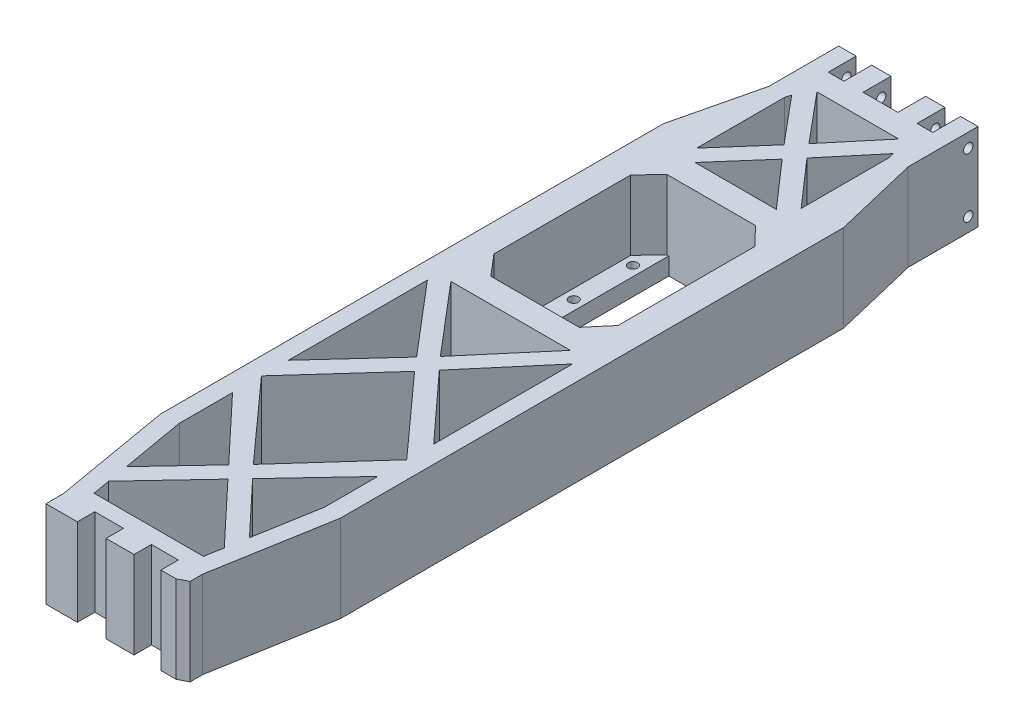
SolidWorks part; units mm, degrees
material "ABS"
ref_plane "Płaszczyzna przednia" through (0, 0, 0) normal (0, 0, 1) x (1, 0, 0)
ref_plane "Płaszczyzna górna" through (0, 0, 0) normal (0, 1, 0) x (1, 0, 0)
ref_plane "Płaszczyzna prawa" through (0, 0, 0) normal (1, 0, 0) x (0, 0, -1)
sketch "Szkic1" plane through (0, 0, 0) normal (0, 1, 0) x (1, 0, 0)
  line L0 (10, 165.9692) -> (14.5, 165.9692)
  line L1 (-0.5, 106.3963) -> (-0.5, -48.6037) construction
  line L2 (-5.4951, 173.9692) -> (-5.4951, 165.9692)
  line L3 (-5.4951, 165.9692) -> (4.4951, 165.9692)
  line L4 (19.5, -48.6037) -> (-20.5, -48.6037)
  line L5 (-11, 173.9692) -> (-5.4951, 173.9692)
  line L6 (25.3521, 129.4864) -> (25.3521, -14.9151)
  line L7 (-11, 173.9692) -> (-11, 165.9692)
  line L8 (14.5, 165.9692) -> (14.5, 173.9692)
  line L9 (-12.7, 117.3963) -> (11.7, 117.3963)
  line L10 (-20.5, 153.94) -> (-26.3521, 129.4864)
  line L11 (14.5, 173.9692) -> (19.5, 173.9692)
  line L12 (-37.6655, 105.3963) -> (36.6655, 105.3963) construction
  line L13 (-0.5, 105.3963) -> (-0.5, 211.3963) construction
  line L14 (11.7, 117.3963) -> (11.7, 72.3963)
  line L15 (11.7, 72.3963) -> (-12.7, 72.3963)
  line L16 (19.5, 173.9692) -> (19.5, 153.94)
  line L17 (-13.2, 117.3963) -> (12.2, 117.3963)
  line L18 (-26.3521, 105.3963) -> (25.3521, 105.3963) construction
  line L19 (1.0907, -6.7501) -> (1.0723, -6.7223)
  line L20 (17.3, 112.0706) -> (17.3, 72.7963)
  line L21 (-20.5, 173.9692) -> (-20.5, 153.94)
  line L22 (19.5, 153.94) -> (25.3521, 129.4864)
  line L23 (10, 173.9692) -> (10, 165.9692)
  line L24 (10, 173.9692) -> (4.4951, 173.9692)
  line L25 (17.3, 72.7963) -> (12.2, 66.7963)
  line L26 (4.4951, 173.9692) -> (4.4951, 165.9692)
  line L27 (12.2, 66.7963) -> (-13.2, 66.7963)
  line L28 (12.2, 117.3963) -> (17.3, 112.0706)
  line L29 (-13.2, 117.3963) -> (-18.3, 112.0706)
  line L30 (-18.3, 72.7963) -> (-13.2, 66.7963)
  line L31 (-18.3, 112.0706) -> (-18.3, 72.7963)
  line L32 (-12.7, 117.3963) -> (-12.7, 72.3963)
  line L33 (19.5, -48.6037) -> (25.3521, -14.9151)
  line L34 (-15.5, 173.9692) -> (-20.5, 173.9692)
  line L35 (-15.5, 165.9692) -> (-15.5, 173.9692)
  line L36 (1.1229, -6.7586) -> (1.0907, -6.7501)
  line L37 (-11, 165.9692) -> (-15.5, 165.9692)
  line L38 (-20.5, -48.6037) -> (-26.3521, -14.9151)
  line L39 (-26.3521, 129.4864) -> (-26.3521, -14.9151)
  line L46 (-2.1229, -6.7586) -> (-2.0907, -6.7501)
  circle A0 centre (14.5, 109.8963) radius 1.35
  circle A1 centre (-0.5, 105.3963) radius 4
  circle A2 centre (14.5, 92.8963) radius 1.35
  circle A3 centre (14.5, 75.8963) radius 1.35
  circle A4 centre (8, 69.5963) radius 1.35
  circle A5 centre (-9, 69.5963) radius 1.35
  circle A7 centre (-15.5, 75.8963) radius 1.35
  circle A8 centre (-15.5, 92.8963) radius 1.35
  circle A9 centre (-15.5, 109.8963) radius 1.35
  point P9 (-15.5208, -48.1484)
  point P12 (0, 85)
  point P14 (-0.5, 156.3785)
  point P16 (-0.5, -39.3616)
  point P18 (-34.2569, 59.805)
  point P22 (-0.5, 105.3963)
  point P24 (-0.5, 176.9822)
  point P27 (32.5, 54.0178)
  point P34 (-0.5, 105.3963)
  point P41 (-0.5, 148.8753)
  point P44 (-0.5, 211.3963)
  point P45 (-9.988, 152.4054)
  point P47 (-36.488, 132.4054)
  point P71 (-0.5, 66.7963)
  point P73 (-0.5, 72.3963)
  point P74 (-0.5, 117.3963)
  point P80 (-0.5, 165.9692)
  point P89 (14.5208, -48.1484)
  dimension "D6" = 45
  dimension "D5" = 12.2
  dimension "D8" = 15
  dimension "D4" = 154
  dimension "D13" = 9.3
  dimension "D14" = 7.5
  dimension "D15" = 8
  dimension "D16" = 1.0723
  dimension "D17" = 1.0907
  dimension "D10" = 2.7
  dimension "D21" = 2.8
  dimension "D26" = 2.7
  dimension "D27" = 2.7
  dimension "D35" = 2.7
  dimension "D9" = 8
  dimension "D11" = 17.8
  dimension "D18" = 1.1229
  dimension "D20" = 5
  dimension "D22" = 4.5
  dimension "D25" = 85
  dimension "D28" = 2.0907
  dimension "D29" = 2.1229
  dimension "D31" = 156.3785
  dimension "D32" = 176.9822
  dimension "D33" = 6.7223
  dimension "D34" = 39.3616
  dimension "D36" = 24.5
  dimension "D37" = 41.5
  dimension "D38" = 47.8
  dimension "D39" = 5.3257
  dimension "D40" = 12.7
  dimension "D7" = 12
extrude "Dodanie-wyciągnięcie1" add sketch "Szkic1" along normal blind 5 contours A2 A0 A1 | L4 L6 region at (-0.5, 0, -53.4364) region at (-13.3187, 0, -94.8963)
extrude "Dodanie-wyciągnięcie2" add sketch "Szkic1<3>" along normal blind 25 contours L4 L6 region at (-0.5, 0, -53.4364)
sketch "Szkic1<3>" plane through (0, 0, 0) normal (0, 1, 0) x (1, 0, 0) same geometry as "Szkic1"
sketch "Szkic6" plane through (0, 25, 0) normal (0, 1, 0) x (1, 0, 0)
  line L2 (25.3521, 129.4864) -> (25.3521, -14.9151) construction
  line L6 (-17.6536, 59.7963) -> (16.6536, 59.7963)
  line L7 (20.3521, -14.4841) -> (15.2068, -44.1037)
  line L9 (20.3521, 152.4805) -> (20.3521, -14.4841)
  line L10 (20.3521, 56.7447) -> (2.7636, 36.0523)
  line L11 (-0.5, 32.2128) -> (20.3521, 9.099)
  line L12 (20.3521, 9.099) -> (-0.5, -14.0721)
  line L13 (16.6536, 59.7963) -> (-0.5, 39.6157)
  line L14 (-15.5, 159.4692) -> (14.5, 159.4692)
  line L15 (14.5, 159.4692) -> (14.5, 124.3963)
  line L16 (20.3521, 0.8026) -> (2.9318, -17.7213)
  line L17 (2.7636, 36.0523) -> (20.3521, 16.8487)
  line L18 (14.5, 124.3963) -> (-15.5, 124.3963)
  line L21 (-16.2068, -44.1037) -> (15.2068, -44.1037)
  line L22 (-15.0864, 155.0784) -> (-15.5, 153.3501)
  line L24 (2.9318, -17.7213) -> (17.1613, -32.8523)
  line L25 (-21.3521, 152.4805) -> (-21.3521, -14.4841)
  line L26 (-0.5, -21.3706) -> (16.0912, -39.0129)
  line L27 (-21.3521, -14.4841) -> (-16.2068, -44.1037)
  line L28 (-0.5, -21.3706) -> (14.805, -37.6453)
  line L29 (11.2406, 159.4692) -> (-0.5, 145.434)
  line L30 (-0.5, 137.7414) -> (11.178, 124.3963)
  line L31 (14.5, 155.5728) -> (2.79, 141.5743)
  line L32 (2.79, 141.5743) -> (14.5, 128.1926)
  line L33 (-15.5, 159.4692) -> (-15.5, 124.3963)
  line L34 (-0.5, -21.3706) -> (-15.805, -37.6453)
  line L35 (-0.5, -21.3706) -> (-17.0912, -39.0129)
  line L36 (-3.9318, -17.7213) -> (-18.1613, -32.8523)
  line L37 (-3.7636, 36.0523) -> (-21.3521, 16.8487)
  line L38 (-0.5, 137.7414) -> (-12.178, 124.3963)
  line L39 (-3.79, 141.5743) -> (-15.5, 128.1926)
  line L40 (-15.5, 155.5728) -> (-3.79, 141.5743)
  line L41 (-12.2406, 159.4692) -> (-0.5, 145.434)
  line L42 (-21.3521, 0.8026) -> (-3.9318, -17.7213)
  line L43 (-17.6536, 59.7963) -> (-0.5, 39.6157)
  line L44 (-21.3521, 9.099) -> (-0.5, -14.0721)
  line L45 (-0.5, 32.2128) -> (-21.3521, 9.099)
  line L46 (-21.3521, 56.7447) -> (-3.7636, 36.0523)
  line L50 (-20.5, 153.94) -> (-26.3521, 129.4864) construction
  line L51 (-0.5, 159.4692) -> (-0.5, 124.3963) construction
  line L52 (14.0864, 155.0784) -> (14.5, 153.3501)
  point P48 (12.5825, 161.0733)
  point P51 (-3.79, 141.501)
  point P52 (12.6186, 122.75)
  point P53 (16.4175, 157.8651)
  point P55 (16.3814, 126.0427)
  point P61 (-0.5, 124.3963)
  point P62 (-0.5, 159.4692)
  dimension "D3" = 8.6985
  dimension "D2" = 5
  dimension "D4" = 8.9707
  dimension "D5" = 9.2609
  dimension "D6" = 10.1453
  dimension "D7" = 10.547
  dimension "D8" = 10.8521
  dimension "D9" = 12.7335
  dimension "D10" = 12.7696
  dimension "D11" = 14.1115
  dimension "D12" = 14.1741
  dimension "D13" = 22.5621
  dimension "D14" = 22.5885
  dimension "D15" = 25.8521
  dimension "D16" = 37.5927
  dimension "D17" = 10.6794
  dimension "D18" = 12.3257
  dimension "D19" = 13.972
  dimension "D20" = 16.122
  dimension "D21" = 33.3634
  dimension "D22" = 40.4099
  dimension "D23" = 5
  dimension "D26" = 43.5022
  dimension "D29" = 52.2743
extrude "Wytnij-wyciągnięcie5" cut sketch "Szkic6" against normal through all contours L6 L43 L13 | L10 L17 L9 | L11 L45 L44 L12 | L46 L25 L37 | L42 L25 L27 L36 | L34 L35 L27 L21 L7 L26 | L16 L24 L7 L9 | L51 L14 L41 | L40 L22 L33 L39 | L51 L38 L18 | L30 L51 L18 | L52 L31 L32 L15 | L14 L51 L29 region at (-0.5, 25, -53.0694) region at (-15.4893, 25, -36.5486) region at (14.4893, 25, -36.5486) region at (13.9735, 25, 16.499) region at (-0.5, 25, 36.1545) region at (-0.5, 25, -9.0799) region at (-14.9735, 25, 16.499) region at (-4.4135, 25, -154.7908) region at (3.4135, 25, -154.7908) region at (-11.5858, 25, -141.7429) region at (-4.3927, 25, -128.8447) region at (3.3927, 25, -128.8447) region at (10.5858, 25, -141.7429)
sketch "Szkic7" plane through (-20.5, 0, 0) normal (-1, 0, 0) x (0, 0, 1)
  line L0 (-173.9692, 25) -> (-168.3692, 25)
  line L1 (-173.9692, 25) -> (-153.94, 25) construction
  line L2 (-173.9692, 12.5) -> (-165.8425, 12.5) construction
  line L3 (-173.9692, 25) -> (-173.9692, 0) construction
  circle A0 centre (-171.1692, 21) radius 1.35
  circle A1 centre (-171.1692, 4) radius 1.35
  point P11 (-169.9059, 12.5)
  dimension "D2" = 2.7
  dimension "D4" = 8.5
  dimension "D1" = 5.6
  dimension "D3" = 2.8
extrude "Wytnij-wyciągnięcie6" cut sketch "Szkic7" against normal through all contours A0 | A1 region at (-20.5, 21, -171.1692) region at (-20.5, 4, -171.1692)
sketch "Szkic8" plane through (0, 25, 0) normal (0, 1, 0) x (1, 0, 0)
  line L0 (19.5, -48.6037) -> (19.5, -52.2555)
  line L1 (16.83, -53.6037) -> (12.5, -53.6037)
  line L2 (12.5, -53.6037) -> (12.5, -48.6037)
  line L3 (19.5, -48.6037) -> (-20.5, -48.6037) construction
  line L4 (12.5, -48.6037) -> (4.7588, -48.6037)
  line L5 (4.7588, -48.6037) -> (4.7588, -53.6037)
  line L6 (4.7588, -53.6037) -> (-3.2412, -53.6037)
  line L7 (-3.2412, -53.6037) -> (-3.2412, -48.6037)
  line L8 (-3.2412, -48.6037) -> (-11.5, -48.6037)
  line L9 (-11.5, -48.6037) -> (-11.5, -53.6037)
  line L10 (-11.5, -53.6037) -> (-20.5, -53.6037)
  line L11 (-20.5, -53.6037) -> (-20.5, -48.6037)
  line L12 (19.5, -48.6037) -> (-20.5, -48.6037)
  line L13 (19.5, -52.2555) -> (16.83, -53.6037)
  line L34 (-20.5, 153.94) -> (-26.3521, 129.4864)
  line L35 (-26.3521, 129.4864) -> (-26.3521, -14.9151)
  line L36 (-26.3521, -14.9151) -> (-20.5, -48.6037)
  line L37 (-20.5, -48.6037) -> (19.5, -48.6037)
  line L38 (19.5, -48.6037) -> (25.3521, -14.9151)
  line L39 (25.3521, -14.9151) -> (25.3521, 129.4864)
  line L40 (25.3521, 129.4864) -> (19.5, 153.94)
  line L41 (19.5, 153.94) -> (19.5, 173.9692)
  line L42 (19.5, 173.9692) -> (14.5, 173.9692)
  line L43 (14.5, 173.9692) -> (14.5, 165.9692)
  line L44 (14.5, 165.9692) -> (10, 165.9692)
  line L45 (10, 165.9692) -> (10, 173.9692)
  line L46 (10, 173.9692) -> (4.4951, 173.9692)
  line L47 (4.4951, 173.9692) -> (4.4951, 165.9692)
  line L48 (4.4951, 165.9692) -> (-5.4951, 165.9692)
  line L49 (-5.4951, 165.9692) -> (-5.4951, 173.9692)
  line L50 (-5.4951, 173.9692) -> (-11, 173.9692)
  line L51 (-11, 173.9692) -> (-11, 165.9692)
  line L52 (-11, 165.9692) -> (-15.5, 165.9692)
  line L53 (-15.5, 165.9692) -> (-15.5, 173.9692)
  line L54 (-15.5, 173.9692) -> (-20.5, 173.9692)
  line L55 (-20.5, 173.9692) -> (-20.5, 153.94)
  line L56 (-20.5, 153.94) -> (-26.3521, 129.4864)
  line L57 (-26.3521, 129.4864) -> (-26.3521, -14.9151)
  line L58 (-26.3521, -14.9151) -> (-20.5, -48.6037)
  line L60 (19.5, -48.6037) -> (25.3521, -14.9151)
  line L61 (25.3521, -14.9151) -> (25.3521, 129.4864)
  line L62 (25.3521, 129.4864) -> (19.5, 153.94)
  line L63 (19.5, 153.94) -> (19.5, 173.9692)
  line L64 (19.5, 173.9692) -> (14.5, 173.9692)
  line L65 (14.5, 173.9692) -> (14.5, 165.9692)
  line L66 (14.5, 165.9692) -> (10, 165.9692)
  line L67 (10, 165.9692) -> (10, 173.9692)
  line L68 (10, 173.9692) -> (4.4951, 173.9692)
  line L69 (4.4951, 173.9692) -> (4.4951, 165.9692)
  line L70 (4.4951, 165.9692) -> (-5.4951, 165.9692)
  line L71 (-5.4951, 165.9692) -> (-5.4951, 173.9692)
  line L72 (-5.4951, 173.9692) -> (-11, 173.9692)
  line L73 (-11, 173.9692) -> (-11, 165.9692)
  line L74 (-11, 165.9692) -> (-15.5, 165.9692)
  line L75 (-15.5, 165.9692) -> (-15.5, 173.9692)
  line L76 (-15.5, 173.9692) -> (-20.5, 173.9692)
  line L77 (-20.5, 173.9692) -> (-20.5, 153.94)
  point P1 (19.5, -53.6037)
  dimension "D1" = 5
  dimension "D2" = 7
  dimension "D3" = 8
  dimension "D4" = 9
  dimension "D5" = 0
  dimension "D6" = 153.21
  dimension "D7" = 4.33
extrude "Dodanie-wyciągnięcie3" add sketch "Szkic8" against normal blind 25 contours L0 L12 L2 L1 | L5 L12 L7 L6 | L9 L12 L11 L10 region at (15.8585, 25, 50.9925) region at (0.7588, 25, 51.1037) region at (-16, 25, 51.1037)
